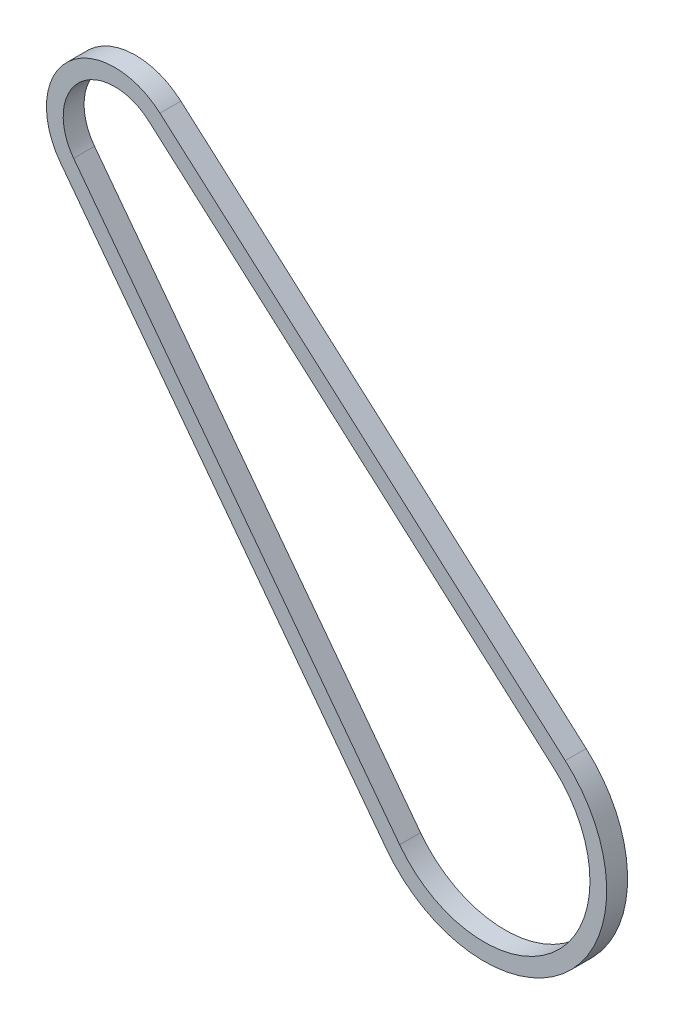
SolidWorks part; units mm, degrees
ref_plane "Front" through (0, 0, 0) normal (0, 0, 1) x (1, 0, 0)
ref_plane "Top" through (0, 0, 0) normal (0, 1, 0) x (1, 0, 0)
ref_plane "Right" through (0, 0, 0) normal (1, 0, 0) x (0, 0, -1)
sketch "Sketch1" plane through (0, 0, 0) normal (0, 0, 1) x (1, 0, 0)
  line L0 (-34.1376, -18.0273) -> (-133.176, 113.0355)
  line L1 (20.2247, 32.3291) -> (-102.8888, 141.0908)
  line L2 (-30.0846, -14.9646) -> (-129.123, 116.0982)
  line L3 (16.8614, 28.5219) -> (-106.2522, 137.2837)
  circle A0 centre (-116.6242, 125.543) radius 20.746 construction
  arc A1 (-34.1376, -18.0273) -> (20.2247, 32.3291) centre (-4.4289, 4.4223) ccw
  arc A3 (-102.8888, 141.0908) -> (-133.176, 113.0355) centre (-116.6242, 125.543) ccw
  arc A4 (-106.2522, 137.2837) -> (-129.123, 116.0982) centre (-116.6242, 125.543) ccw
  arc A5 (-30.0846, -14.9646) -> (16.8614, 28.5219) centre (-4.4289, 4.4223) ccw
  dimension "D1" = 5.08
extrude "Boss-Extrude1" add sketch "Sketch1" along normal blind 6.35
